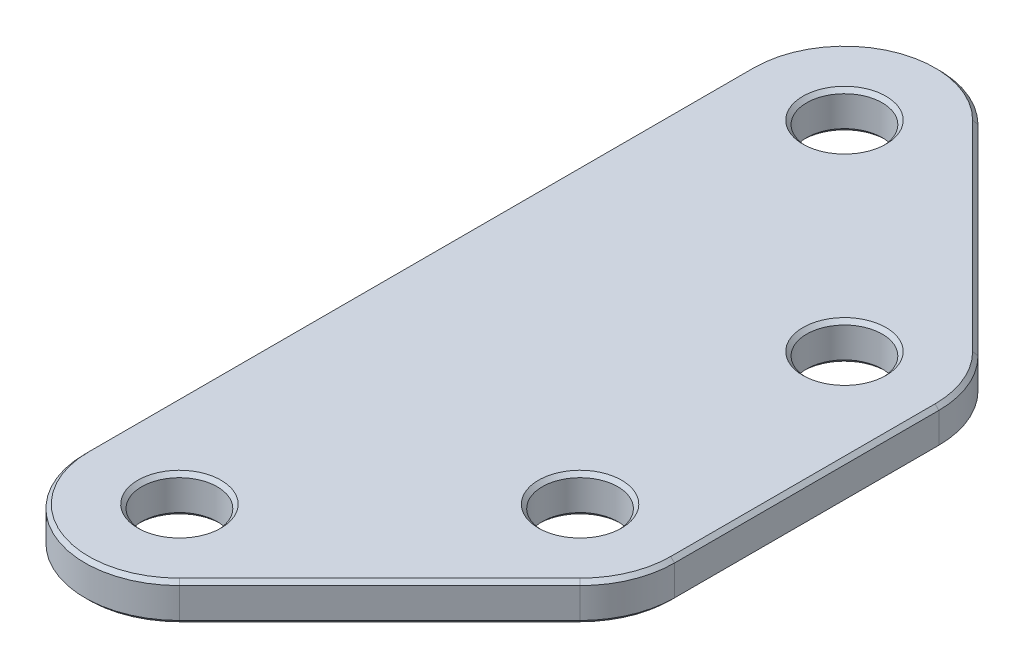
SolidWorks part; units mm, degrees
ref_plane "Front Plane" through (0, 0, 0) normal (0, 0, 1) x (1, 0, 0)
ref_plane "Top Plane" through (0, 0, 0) normal (0, 1, 0) x (1, 0, 0)
ref_plane "Right Plane" through (0, 0, 0) normal (1, 0, 0) x (0, 0, -1)
sketch "Sketch1" plane through (0, 0, 0) normal (0, 1, 0) x (1, 0, 0)
  line L0 (0, 0) -> (-100, 0) construction
  line L1 (-50, 176.066) -> (-50, -176.066) construction
  line L2 (-50, -176.066) -> (56.066, -70) construction
  line L3 (56.066, -70) -> (56.066, 70) construction
  line L4 (56.066, 70) -> (-50, 176.066) construction
  line L5 (-100, 176.066) -> (-100, -176.066)
  line L6 (-14.6447, -211.4214) -> (91.4214, -105.3553)
  line L7 (106.066, -70) -> (106.066, 70)
  line L8 (91.4214, 105.3553) -> (-14.6447, 211.4214)
  line L9 (56.066, -70) -> (139.4899, -104.5553) construction
  line L10 (56.066, 70) -> (143.1211, 106.0594) construction
  circle A0 centre (-50, 176.066) radius 20
  circle A1 centre (56.066, 70) radius 20
  circle A2 centre (56.066, -70) radius 20
  circle A3 centre (-50, -176.066) radius 20
  arc A4 (-100, -176.066) -> (-14.6447, -211.4214) centre (-50, -176.066) ccw
  arc A5 (91.4214, -105.3553) -> (106.066, -70) centre (56.066, -70) ccw
  arc A6 (106.066, 70) -> (91.4214, 105.3553) centre (56.066, 70) ccw
  arc A7 (-100, 176.066) -> (-14.6447, 211.4214) centre (-50, 176.066) cw
  point P11 (97.6166, 136.3511)
  point P12 (-50, 0)
  point P16 (80.7107, -120)
  point P17 (80.7107, 120)
  point P25 (106.066, -90.7107)
  point P28 (106.066, 90.7107)
  dimension "D3" = 40
  dimension "D4" = 40
  dimension "D5" = 40
  dimension "D6" = 40
  dimension "D15" = 50
  dimension "D1" = 135
  dimension "D2" = 135
  dimension "D7" = 150
  dimension "D8" = 140
  dimension "D9" = 50
  dimension "D10" = 225
  dimension "D11" = 225
  dimension "D12" = 50
  dimension "D13" = 112.5
  dimension "D14" = 112.5
extrude "Boss-Extrude1" add sketch "Sketch1" along normal blind 20
chamfer "Chamfer1" distance 2 angle 45 24 edges at (56.066, 0, -50) (56.066, 20, -50) (-50, 0, 196.066) (-50, 20, 196.066) (56.066, 0, 90) (56.066, 20, 90) (-50, 0, -156.066) (-50, 20, -156.066) (38.3883, 0, 158.3883) (102.26, 0, 89.1342) (106.066, 0, 0) (102.26, 0, -89.1342) (38.3883, 0, -158.3883) (-69.1342, 0, -222.26) (-100, 0, 0) (-69.1342, 0, 222.26) (-100, 20, 0) (-69.1342, 20, -222.26) (38.3883, 20, -158.3883) (102.26, 20, -89.1342) (106.066, 20, 0) (102.26, 20, 89.1342) (38.3883, 20, 158.3883) (-69.1342, 20, 222.26)
